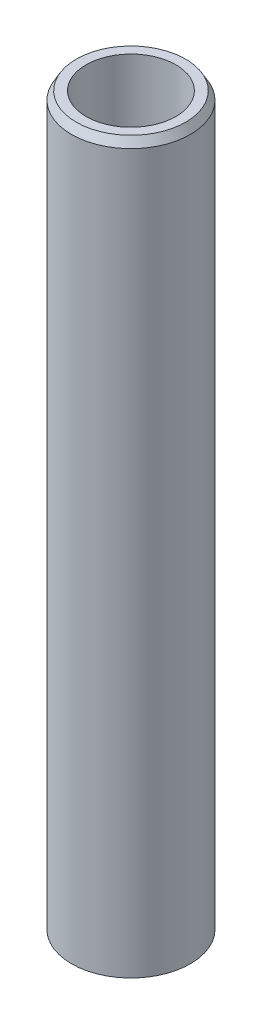
SolidWorks part; units mm, degrees
ref_plane "Front Plane" through (0, 0, 0) normal (0, 0, 1) x (1, 0, 0)
ref_plane "Top Plane" through (0, 0, 0) normal (0, 1, 0) x (1, 0, 0)
ref_plane "Right Plane" through (0, 0, 0) normal (1, 0, 0) x (0, 0, -1)
sketch "Sketch1" plane through (0, 0, 0) normal (0, 1, 0) x (1, 0, 0)
  circle A0 centre (0, 0) radius 32.5
  dimension "SHAFT_OD" = 65
extrude "Boss-Extrude1" add sketch "Sketch1" along normal blind 399.8609
sketch "Sketch2" plane through (0, 0, 0) normal (0, 1, 0) x (1, 0, 0)
  circle A0 centre (0, 0) radius 24.5361
  dimension "BORE_D" = 49.0722
extrude "Cut-Extrude1" cut sketch "Sketch2" along normal through all
chamfer "Chamfer1" distance 4.4992 angle 30 2 edges at (0, 399.8609, 32.5) (0, 0, 32.5) first distance on face at (0, 399.8609, 32.5) first distance on face at (0, 0, 24.5361)
